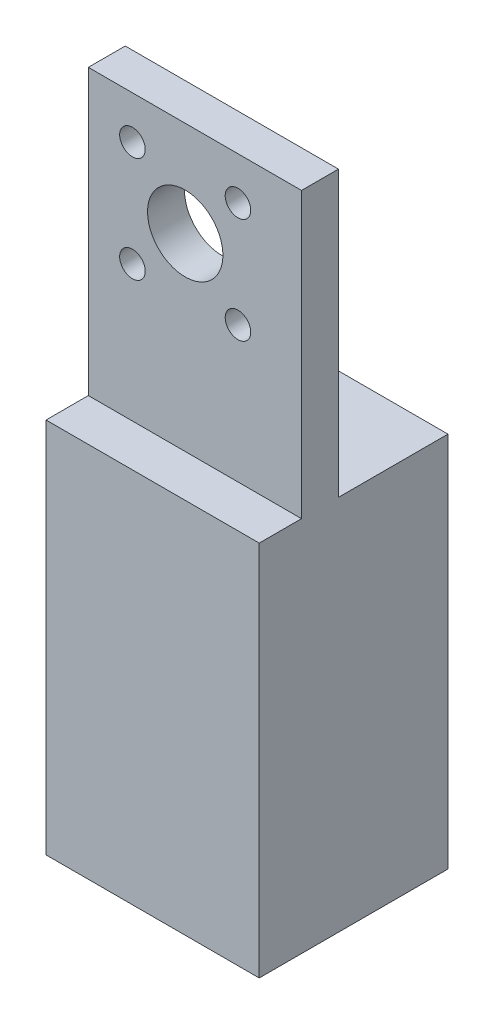
SolidWorks part; units mm, degrees
ref_plane "Alzado" through (0, 0, 0) normal (0, 0, 1) x (1, 0, 0)
ref_plane "Planta" through (0, 0, 0) normal (0, 1, 0) x (1, 0, 0)
ref_plane "Vista lateral" through (0, 0, 0) normal (1, 0, 0) x (0, 0, -1)
sketch "Croquis1" plane through (0, 0, 0) normal (0, 1, 0) x (1, 0, 0)
  line L1 (-15, 13.2786) -> (15, 13.2786)
  line L2 (-15, 13.2786) -> (-15, -13.2786)
  line L3 (-15, -13.2786) -> (15, -13.2786)
  line L4 (15, 13.2786) -> (15, -13.2786)
  line L5 (-15, 13.2786) -> (15, -13.2786) construction
  line L6 (-15, -13.2786) -> (15, 13.2786) construction
  line L7 (-12, 10.6229) -> (12, 10.6229)
  line L8 (-12, 10.6229) -> (-12, -10.6229)
  line L9 (-12, -10.6229) -> (12, -10.6229)
  line L10 (12, 10.6229) -> (12, -10.6229)
  line L11 (-12, 10.6229) -> (12, -10.6229) construction
  line L12 (-12, -10.6229) -> (12, 10.6229) construction
  point P0 (0, 0)
  point P6 (0, 0)
  dimension "D1" = 30
  dimension "D2" = 3
extrude "Saliente-Extruir1" add sketch "Croquis1" along normal blind 50
sketch "Croquis2" plane through (0, 50, 0) normal (0, 1, 0) x (1, 0, 0)
  line L1 (-15, 13.2786) -> (15, 13.2786)
  line L2 (-15, 13.2786) -> (-15, -13.2786)
  line L3 (-15, -13.2786) -> (15, -13.2786)
  line L4 (15, 13.2786) -> (15, -13.2786)
extrude "Saliente-Extruir2" add sketch "Croquis2" along normal blind 3
sketch "Croquis3" plane through (0, 53, 0) normal (0, 1, 0) x (1, 0, 0)
  line L0 (-15, 13.2786) -> (-15, -13.2786) construction
  line L1 (-15, -7.3282) -> (15, -7.3282)
  line L2 (-15, -7.3282) -> (-15, -2.1315)
  line L3 (-15, -2.1315) -> (15, -2.1315)
  line L4 (15, -7.3282) -> (15, -2.1315)
  line L5 (15, -13.2786) -> (15, 13.2786) construction
extrude "Saliente-Extruir3" add sketch "Croquis3" along normal blind 40
sketch "Croquis4" plane through (0, 0, 2.1315) normal (0, 0, -1) x (-1, 0, 0)
  line L0 (1.3656, 79.5682) -> (11.8656, 79.5682) construction
  line L1 (1.3656, 79.5682) -> (8.7902, 86.9928) construction
  circle A0 centre (1.3656, 79.5682) radius 10.5 construction
  circle A1 centre (8.7902, 86.9928) radius 1.8
  circle A2 centre (8.7902, 72.1436) radius 1.8
  circle A3 centre (-6.0591, 72.1436) radius 1.8
  circle A4 centre (-6.0591, 86.9928) radius 1.8
  circle A5 centre (1.3656, 79.5682) radius 5.3
  point P14 (1.3656, 79.5682)
  dimension "D1" = 21
  dimension "D2" = 3.6
  dimension "D5" = 10.6
  dimension "D3" = 45
  dimension "D4" = 4
extrude "Cortar-Extruir1" cut sketch "Croquis4" against normal blind 40
